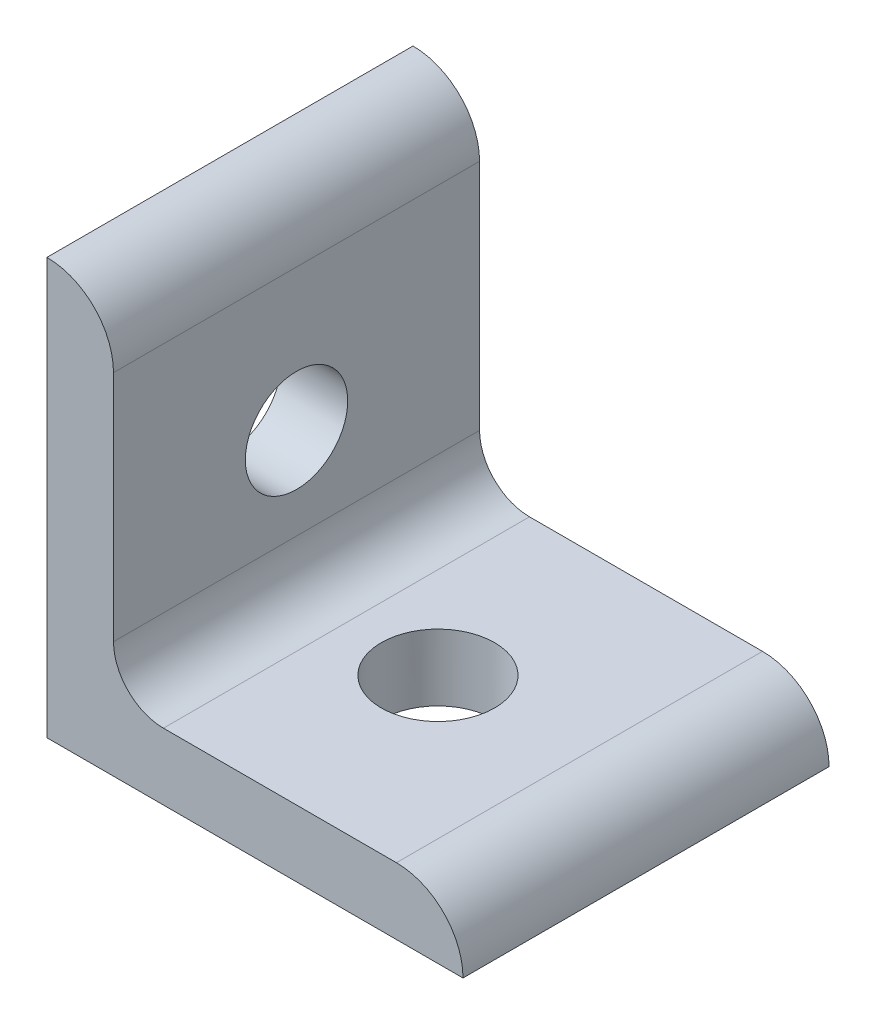
SolidWorks part; units mm, degrees
material "6105-T5 Aluminum"
ref_plane "Front Plane" through (0, 0, 0) normal (0, 0, 1) x (1, 0, 0)
ref_plane "Top Plane" through (0, 0, 0) normal (0, 1, 0) x (1, 0, 0)
ref_plane "Right Plane" through (0, 0, 0) normal (1, 0, 0) x (0, 0, -1)
sketch "Sketch1" plane through (0, 0, 0) normal (0, 0, 1) x (1, 0, 0)
  line L0 (0, 0) -> (0, 25)
  line L1 (0, 25) -> (4, 25)
  line L2 (4, 25) -> (4, 4)
  line L3 (4, 4) -> (25, 4)
  line L4 (25, 4) -> (25, 0)
  line L5 (25, 0) -> (0, 0)
  dimension "D1" = 25
  dimension "D2" = 25
  dimension "D3" = 4
  dimension "D4" = 4
extrude "Boss-Extrude1" add sketch "Sketch1" along normal mid plane 21.9964
fillet "Fillet1" radius 4 2 edges at (25, 4, 0) (4, 25, 0)
fillet "Fillet2" radius 3 1 edges at (4, 4, 0)
sketch "Sketch2" plane through (0, 0, 0) normal (0, -1, 0) x (1, 0, 0)
  line L0 (0, 10.9982) -> (25, 10.9982) construction
  line L2 (0, 10.9982) -> (0, -10.9982) construction
  circle A0 centre (12.4968, 0) radius 3.4036
  dimension "D1" = 6.8072
  dimension "D2" = 10.9982
  dimension "D3" = 12.4968
extrude "Cut-Extrude1" cut sketch "Sketch2" against normal up to next
sketch "Sketch4" plane through (0, 0, 0) normal (-1, 0, 0) x (0, 0, 1)
  line L0 (10.9982, 0) -> (-10.9982, 0) construction
  line L1 (10.9982, 25) -> (10.9982, 0) construction
  circle A0 centre (0, 12.4968) radius 3.076
  dimension "D1" = 12.4968
  dimension "D2" = 10.9982
extrude "Cut-Extrude2" cut sketch "Sketch4" against normal up to next
